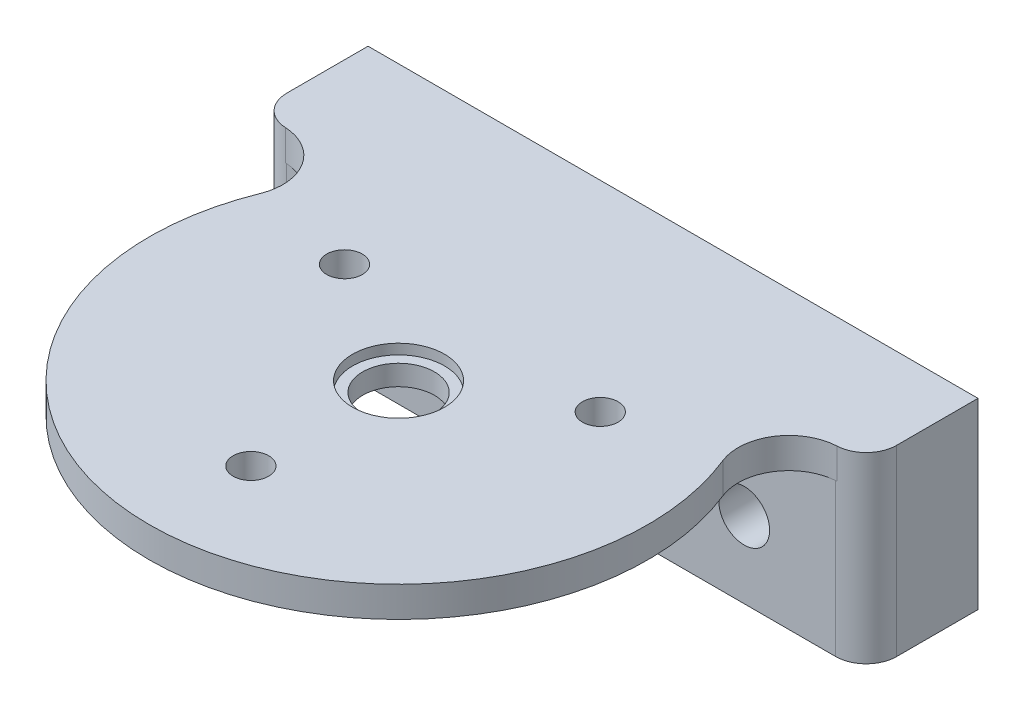
SolidWorks part; units mm, degrees
ref_plane "Front Plane" through (0, 0, 0) normal (0, 0, 1) x (1, 0, 0)
ref_plane "Top Plane" through (0, 0, 0) normal (0, 1, 0) x (1, 0, 0)
ref_plane "Right Plane" through (0, 0, 0) normal (1, 0, 0) x (0, 0, -1)
sketch "Sketch1" plane through (0, 0, 0) normal (0, 1, 0) x (1, 0, 0)
  circle A0 centre (0, 0) radius 4.525
  circle A1 centre (0, 0) radius 3.525
  circle A2 centre (0, 0) radius 24.525
  dimension "D1" = 9.05
  dimension "D2" = 1
  dimension "D3" = 20
extrude "Boss-Extrude1" add sketch "Sketch1" along normal blind 2 contours A0 A1 region at (-4.397, 0, 0)
extrude "Boss-Extrude3" add sketch "Sketch1<5>" along normal offset from surface (3 mm away) 1 contours A2 A0 region at (-23.8313, 0, 0) up to face at (0, 2, 3.525) offset beyond the face yes
sketch "Sketch1<5>" plane through (0, 0, 0) normal (0, 1, 0) x (1, 0, 0) same geometry as "Sketch1"
sketch "Sketch2" plane through (0, 3, 0) normal (0, 1, 0) x (1, 0, 0)
  line L0 (0, -4.525) -> (0, -24.525) construction
  circle A0 centre (0, 0) radius 4.525 construction
  circle A1 centre (0, 0) radius 24.525 construction
  circle A2 centre (0, -14.525) radius 1.75
  dimension "D1" = 3.5
extrude "Cut-Extrude1" cut sketch "Sketch2" against normal blind 4.5
pattern_circular "CirPattern1" count 3 over 360 about axis through (0, 2, 0) along (0, -1, 0) of "Cut-Extrude1"
sketch "Sketch9" plane through (0, 0, 0) normal (0, -1, 0) x (1, 0, 0)
  line L2 (-30, -27) -> (30, -27)
  line L4 (-30, -16) -> (30, -16)
  line L5 (-30, -27) -> (-30, -16)
  line L6 (30, -27) -> (30, -16)
  line L7 (0, 0) -> (0, -27) construction
  line L8 (0, -27) -> (-30, -27) construction
  point P7 (0, -16)
  dimension "D1" = 16
  dimension "D2" = 11
  dimension "D4" = 30
extrude "Boss-Extrude7" add sketch "Sketch9" along normal blind 15 and the other way up to surface (3 mm away) other way up to face at (-14.0946, 3, -8.1375)
sketch "Sketch10" plane through (0, 0, -16) normal (0, 0, 1) x (1, 0, 0)
  line L0 (0, 0) -> (0, -15) construction
  line L3 (-18, -7.5) -> (0, -7.5) construction
  line L5 (30, -15) -> (-30, -15) construction
  line L6 (-18.587, 0) -> (18.587, 0) construction
  circle A0 centre (-18, -7.5) radius 2.5
  circle A2 centre (18, -7.5) radius 2.5
  point P11 (0, -15)
  point P15 (0, 0)
  dimension "D2" = 5
  dimension "D1" = 18
extrude "Cut-Extrude3" cut sketch "Sketch10" against normal up to next
fillet "Fillet4" radius 3 2 edges at (-30, -6, -16) (30, -6, -16)
fillet "Fillet5" radius 5 2 edges at (18.587, 1.5, -16) (-18.587, 1.5, -16)
